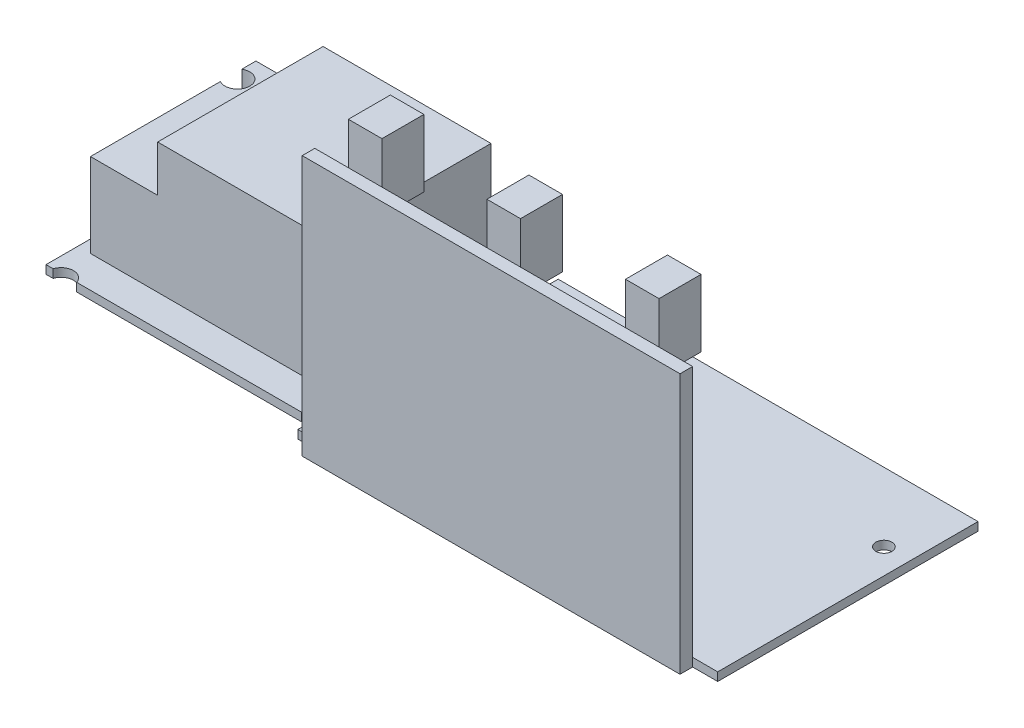
SolidWorks part; units mm, degrees
ref_plane "Plan de face" through (0, 0, 0) normal (0, 0, 1) x (1, 0, 0)
ref_plane "Plan de dessus" through (0, 0, 0) normal (0, 1, 0) x (1, 0, 0)
ref_plane "Plan de droite" through (0, 0, 0) normal (1, 0, 0) x (0, 0, -1)
sketch "Esquisse2" plane through (0, 0, 0) normal (0, 1, 0) x (1, 0, 0)
  line L0 (-46.6357, 0.782) -> (36.3643, 0.782) construction
  line L1 (36.3643, 0.782) -> (36.3643, -27.218) construction
  line L2 (36.3643, -27.218) -> (3.3643, -27.218) construction
  line L3 (3.3643, -27.218) -> (3.3643, -30.218) construction
  line L4 (3.3643, -30.218) -> (-46.6357, -30.218) construction
  line L5 (-46.6357, -30.218) -> (-46.6357, 0.782) construction
  line L6 (-46.6357, -30.218) -> (-46.6357, 0.782)
  line L7 (-46.6357, 0.782) -> (3.3643, 0.782)
  line L8 (36.3643, 0.782) -> (36.3643, -27.218)
  line L9 (36.3643, -27.218) -> (3.3643, -27.218)
  line L10 (3.3643, -27.218) -> (3.3643, -30.218)
  line L11 (3.3643, -30.218) -> (-46.6357, -30.218)
  line L12 (3.3643, -30.218) -> (1.3514, -30.218) construction
  line L13 (1.3514, -30.218) -> (1.3514, -31.718) construction
  line L14 (1.3514, -31.718) -> (-43.6486, -31.718) construction
  line L15 (-43.6486, -31.718) -> (-43.6486, -30.218) construction
  line L16 (-43.6486, -30.218) -> (-43.6486, -31.718)
  line L17 (-43.6486, -31.718) -> (1.3514, -31.718)
  line L18 (1.3514, -31.718) -> (1.3514, -30.218)
  line L19 (6.8643, -23.4207) -> (6.8643, -3.718) construction
  line L20 (6.8643, -3.718) -> (34.8643, -3.718) construction
  line L21 (34.8643, -3.718) -> (34.8643, -23.4207) construction
  line L22 (34.8643, -23.4207) -> (6.8643, -23.4207) construction
  line L23 (26.8643, -23.4207) -> (26.8643, -3.718) construction
  line L24 (3.3643, -1029.9207) -> (3.3643, 48970.0793) construction
  line L25 (26.8643, -23.4207) -> (26.8643, -3.718)
  line L26 (6.8643, -23.4207) -> (34.8643, -23.4207)
  line L27 (6.8643, -23.4207) -> (6.8643, -3.718)
  line L28 (6.8643, -3.718) -> (34.8643, -3.718)
  line L29 (34.8643, -23.4207) -> (34.8643, -3.718)
  line L30 (3.3643, -30.218) -> (3.3643, 0.782)
  line L31 (-966.2008, -6.4207) -> (49033.7992, -6.4207) construction
  line L32 (3.3643, 0.782) -> (36.3643, 0.782)
  line L33 (-43.6357, -1013.5939) -> (-43.6357, 48986.4061) construction
  circle A2 centre (-43.6357, -7.4207) radius 0.9565
  circle A3 centre (34.1143, -27.6707) radius 1.475
  circle A4 centre (34.1143, -6.6707) radius 1.475
  circle A5 centre (4.5341, -27.6707) radius 1.475
  circle A6 centre (34.1143, -6.6707) radius 1.475
  circle A7 centre (34.1143, -6.6707) radius 1.475
  circle A8 centre (34.1143, -27.6707) radius 1.475
  circle A9 centre (34.1143, -6.6707) radius 1.475
  circle A10 centre (34.1143, -6.6707) radius 1.475
  circle A11 centre (4.5341, -6.6707) radius 1.475
  point P16 (16.4777, 0)
  point P31 (-43.6357, -7.4207)
  dimension "D16" = 3
  dimension "D1" = 50
  dimension "D2" = 31
  dimension "D3" = 33
  dimension "D4" = 3
  dimension "D5" = 1.5
  dimension "D6" = 45
  dimension "D7" = 2.0129
  dimension "D8" = 3.5
  dimension "D9" = 4.5
  dimension "D10" = 28
  dimension "D12" = 8
extrude "Boss.-Extru.4" add sketch "Esquisse2" against normal blind 1 contours A11 L30 L7 L6 L11 L10 A5 A2 region at (-21.6068, 0, 14.7304)
extrude "Boss.-Extru.5" add sketch "Esquisse2<4>" along normal blind 1 separate body contours A11 L30 A5 L9 L8 L7 A4 A3 L29 L26 L27 L28 region at (19.8643, 0, -0.3492)
sketch "Esquisse2<4>" plane through (0, 0, 0) normal (0, 1, 0) x (1, 0, 0) same geometry as "Esquisse2"
extrude "Boss.-Extru.6" add sketch "Esquisse2<5>" against normal blind 10 separate body contours L26 L29 L28 L25 region at (30.7551, 0, 13.8202)
sketch "Esquisse2<5>" plane through (0, 0, 0) normal (0, 1, 0) x (1, 0, 0) same geometry as "Esquisse2"
extrude "Boss.-Extru.7" add sketch "Esquisse2<6>" against normal blind 15.5 contours L28 L27 L26 L25 region at (16.8643, 0, 13.5694)
sketch "Esquisse2<6>" plane through (0, 0, 0) normal (0, 1, 0) x (1, 0, 0) same geometry as "Esquisse2"
extrude "Boss.-Extru.8" add sketch "Esquisse2<7>" against normal blind 31 contours L17 L18 L11 L16 region at (-21.1486, 0, 30.968)
sketch "Esquisse2<7>" plane through (0, 0, 0) normal (0, 1, 0) x (1, 0, 0) same geometry as "Esquisse2"
move or copy body "Corps-Déplacer/Copier1" bodies to move or copy 105 108 107 copy no rotation origin (-5.1357, -15, 0) rotation axis (0, 0, 1) rotation angle 180
sketch "Esquisse3" plane through (0, 0, 30.218) normal (0, 0, -1) x (-1, 0, 0)
  line L0 (-31.5326, -2) -> (17.5209, -2) construction
  line L1 (-25.3773, 6) -> (-25.3773, -38.275) construction
  line L2 (-8.8773, 7.1703) -> (-8.8773, -41.2006) construction
  line L3 (7.6227, 7.0592) -> (7.6227, -40.831) construction
  line L4 (11.6227, 1) -> (-33.3773, 1) construction
  line L5 (-29.3773, 6) -> (-29.3773, -37.2226) construction
  line L6 (-12.8773, 6) -> (-12.8773, -41.2006) construction
  line L7 (3.6232, 7.1197) -> (3.6232, -41.8833) construction
  line L8 (-33.3773, 1) -> (-33.3773, -29) construction
  line L9 (11.6227, 1) -> (11.6227, -29) construction
  line L11 (-29.3773, 6) -> (-25.3773, 6)
  line L12 (-29.3773, 6) -> (-29.3773, -2)
  line L13 (-29.3773, -2) -> (-25.3773, -2)
  line L14 (-25.3773, 6) -> (-25.3773, -2)
  line L15 (-12.8773, 6) -> (-8.8773, 6)
  line L16 (-12.8773, 6) -> (-12.8773, -2)
  line L17 (-12.8773, -2) -> (-8.8773, -2)
  line L18 (-8.8773, 6) -> (-8.8773, -2)
  line L19 (3.6232, 6) -> (7.6227, 6)
  line L20 (3.6232, 6) -> (3.6232, -2)
  line L21 (3.6232, -2) -> (7.6227, -2)
  line L22 (7.6227, 6) -> (7.6227, -2)
  dimension "D1" = 3
  dimension "D2" = 4
  dimension "D3" = 4
  dimension "D4" = 4
  dimension "D5" = 4
  dimension "D6" = 4
  dimension "D7" = 29.0005
  dimension "D8" = 12.5
  dimension "D9" = 8
extrude "Boss.-Extru.9" add sketch "Esquisse3" along normal blind 5
sketch "Esquisse4" plane through (0, -29, 0) normal (0, 1, 0) x (1, 0, 0)
  line L0 (33.3643, -32.9207) -> (33.3643, 8.7631) construction
  line L1 (33.3773, -30.218) -> (36.3643, -30.218) construction
  line L2 (53.475, -10.9207) -> (-57.6025, -10.9207) construction
  line L3 (47.0386, -8.9207) -> (-57.6025, -8.9207) construction
  line L4 (29.3643, 1.0182) -> (29.3643, -35.4907) construction
  line L5 (36.3643, -30.218) -> (36.3643, 0.782) construction
  line L6 (33.3643, -7.4207) -> (33.3643, -9.8792) construction
  line L7 (36.3643, 0.782) -> (-13.6357, 0.782) construction
  line L8 (1.2703, -4.4207) -> (68.7508, -4.4207) construction
  line L9 (34.8708, -32.9207) -> (68.7508, -32.9207) construction
  dimension "D1" = 19.2972
  dimension "D2" = 2
  dimension "D3" = 3
  dimension "D4" = 4
  dimension "D5" = 2.4584
  dimension "D6" = 28.5
